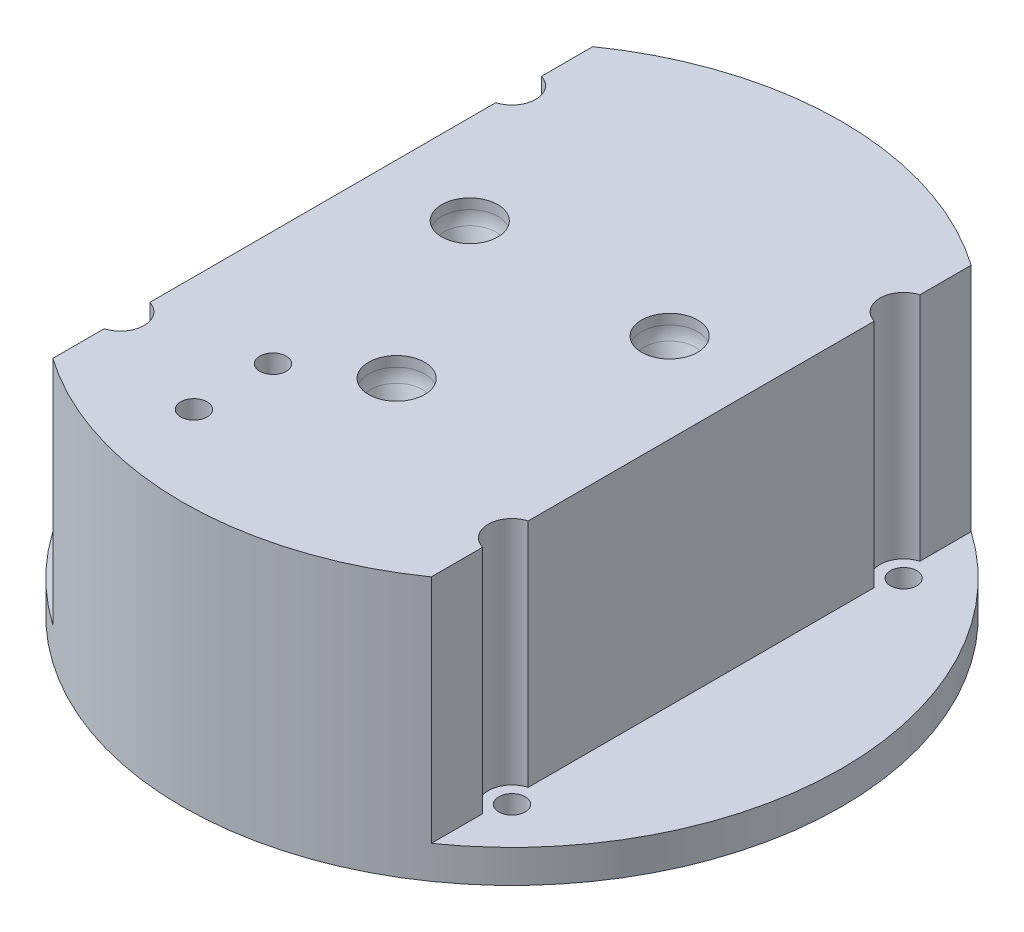
SolidWorks part; units mm, degrees
ref_plane "Ön Düzlem" through (0, 0, 0) normal (0, 0, 1) x (1, 0, 0)
ref_plane "Üst Düzlem" through (0, 0, 0) normal (0, 1, 0) x (1, 0, 0)
ref_plane "Sağ Düzlem" through (0, 0, 0) normal (1, 0, 0) x (0, 0, -1)
sketch "ara düzlem" plane through (0, 0, 0) normal (0, 1, 0) x (1, 0, 0)
  line L0 (-28.7, 40.9428) -> (-28.7, -40.9428)
  line L1 (0, 0) -> (0, 50) construction
  line L2 (28.7, 40.9428) -> (28.7, -40.9428)
  circle A0 centre (0, 0) radius 50
  point P5 (14.6186, 0)
  point P8 (-50, 0)
  point P11 (-28.7, 0)
  dimension "D1" = 100
  dimension "D2" = 21.3
extrude "base" add sketch "ara düzlem" along normal blind 5 contours L0 A0 | L2 A0 L0 | L2 A0 region at (0, 0, 0) region at (-37.3976, 0, 0) region at (37.3976, 0, 0)
extrude "Yükseklik-Ekstrüzyon2" add sketch "Çizim1<3>" along normal blind 40 contours L2 A0 L0 region at (0, 0, 0)
sketch "Çizim1<3>" plane through (0, 0, 0) normal (0, 1, 0) x (1, 0, 0) same geometry as "ara düzlem"
sketch "Çizim2" plane through (0, 40, 0) normal (0, 1, 0) x (1, 0, 0)
  line L0 (-11.3, -30.9428) -> (28.7, -30.9428) construction
  line L2 (28.7, 40.9428) -> (28.7, -40.9428) construction
  circle A0 centre (-11.3, -24.9428) radius 2
  circle A2 centre (-11.3, -36.9428) radius 2
  dimension "D1" = 4
  dimension "D2" = 6
  dimension "D3" = 40
  dimension "D4" = 10
extrude "banana slotları" cut sketch "Çizim2" against normal through all
sketch "Çizim3" plane through (0, 0, 0) normal (0, -1, 0) x (1, 0, 0)
  circle A0 centre (0, 0) radius 42 construction
  circle A1 centre (-29.6985, 29.6985) radius 2
  circle A5 centre (0, 0) radius 50 construction
  circle A6 centre (29.6985, 29.6985) radius 2
  circle A7 centre (29.6985, -29.6985) radius 2
  circle A8 centre (-29.6985, -29.6985) radius 2
  circle A9 centre (0, 0) radius 5.05
  point P16 (0, 0)
  dimension "D1" = 4
  dimension "D2" = 8
  dimension "D4" = 10.1
  dimension "D3" = 4
sketch "Çizim4" plane through (0, 5, 0) normal (0, 1, 0) x (1, 0, 0)
  point P0 (-28.7, 0)
extrude "Kes-Ekstrüzyon1" cut sketch "Çizim3" against normal blind 5
extrude "Kes-Ekstrüzyon2" cut sketch "Çizim3<2>" against normal through all contours A1 | A8 | A7 | A6 region at (-29.6985, 0, 29.6985) region at (29.6985, 0, 29.6985) region at (29.6985, 0, -29.6985) region at (-29.6985, 0, -29.6985)
sketch "Çizim3<2>" plane through (0, 0, 0) normal (0, -1, 0) x (1, 0, 0) same geometry as "Çizim3"
sketch "Çizim5" plane through (0, 5, 0) normal (0, 1, 0) x (1, 0, 0)
  circle A0 centre (29.6985, -29.6985) radius 3.6
  arc A1 (28.7, -31.4314) -> (28.7, -27.9656) centre (29.6985, -29.6985) ccw construction
  circle A2 centre (-29.6985, -29.6985) radius 3.6
  circle A3 centre (-29.6985, 29.6985) radius 3.6
  circle A4 centre (29.6985, 29.6985) radius 3.6
  point P13 (0, 0)
  dimension "D1" = 7.2
  dimension "D2" = 4
extrude "Kes-Ekstrüzyon3" cut sketch "Çizim5" along normal through all
sketch "Çizim6" plane through (0, 40, 0) normal (0, 1, 0) x (1, 0, 0)
  circle A0 centre (0, -17.5) radius 4.25
  point P2 (0, 0)
  point P3 (0, 0)
  point P5 (0, -12.9457)
  dimension "D1" = 8.5
  dimension "D2" = 17.5
extrude "Kes-Ekstrüzyon4" cut sketch "Çizim6" against normal blind 7.5
chamfer "Pah1" distance 5 distance2 2 1 edges at (0, 32.5, 21.75) first distance on face at (0, 32.5, 21.75)
fillet "Radyus1" radius 5 1 edges at (0, 37.5, 21.75)
pattern_circular "Dairesel Kaplama1" count 3 over 360 about axis through (0, 5, 0) along (0, -1, 0) of "Radyus1", "Pah1", "Kes-Ekstrüzyon4"
